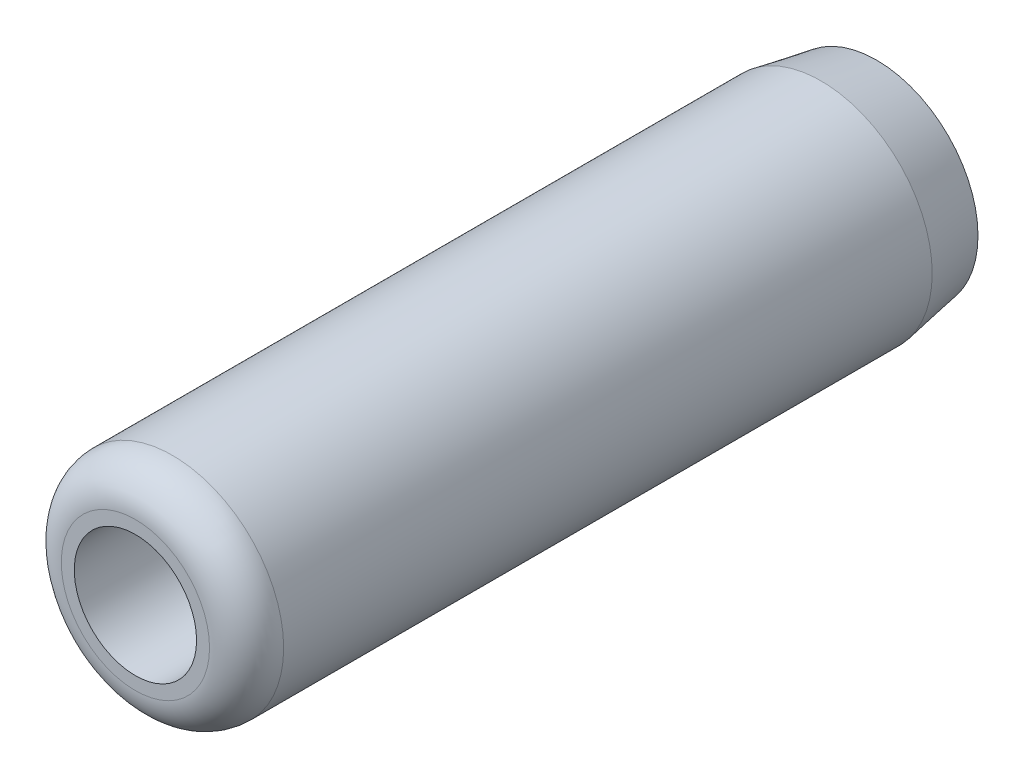
SolidWorks part; units mm, degrees
material "S45C"
ref_plane "正面" through (0, 0, 0) normal (0, 0, 1) x (1, 0, 0)
ref_plane "平面" through (0, 0, 0) normal (0, 1, 0) x (1, 0, 0)
ref_plane "右側面" through (0, 0, 0) normal (1, 0, 0) x (0, 0, -1)
sketch "ｽｹｯﾁ1" plane through (0, 0, 0) normal (1, 0, 0) x (0, 0, -1)
  line L0 (0, 0) -> (129.8709, 0) construction
  line L1 (0, 0) -> (0, 2)
  line L2 (1, 3) -> (18.5, 3)
  line L3 (18.5, 3) -> (20, 2.7355)
  line L4 (20, 2.7355) -> (20, 0)
  line L5 (20, 0) -> (0, 0)
  arc A0 (0, 2) -> (1, 3) centre (1, 2) cw
  dimension "D5" = 1
  dimension "D1" = 10
  dimension "D2" = 20
  dimension "D3" = 6
  dimension "D4" = 1.5
revolve "回転1" add sketch "ｽｹｯﾁ1" angle 360 about L0
hole_wizard "M4 ねじ穴1" positions "ｽｹｯﾁ2" profile "ｽｹｯﾁ3" tap size "M4" standard "JIS" end condition through all
sketch "ｽｹｯﾁ2" plane through (0, 0, 0) normal (0, 0, 1) x (1, 0, 0)
  point P0 (0, 0)
sketch "ｽｹｯﾁ3" plane through (0, 0, 0) normal (1, 0, 0) x (0, -1, 0)
  line L0 (0, 0) -> (0, 20)
  line L1 (0, 20) -> (1.65, 20)
  line L2 (1.65, 20) -> (1.65, 0)
  line L5 (1.65, 0) -> (0, 0)
  line L11 (0, -6.35) -> (0, 107.95) construction
  dimension "次ｻｰﾌｪｽまでのねじ下穴ﾄﾞﾘﾙ直径" = 3.3
  dimension "次ｻｰﾌｪｽまでのねじ下穴ﾄﾞﾘﾙの深さ" = 20
cosmetic thread "穴のねじ山1"
